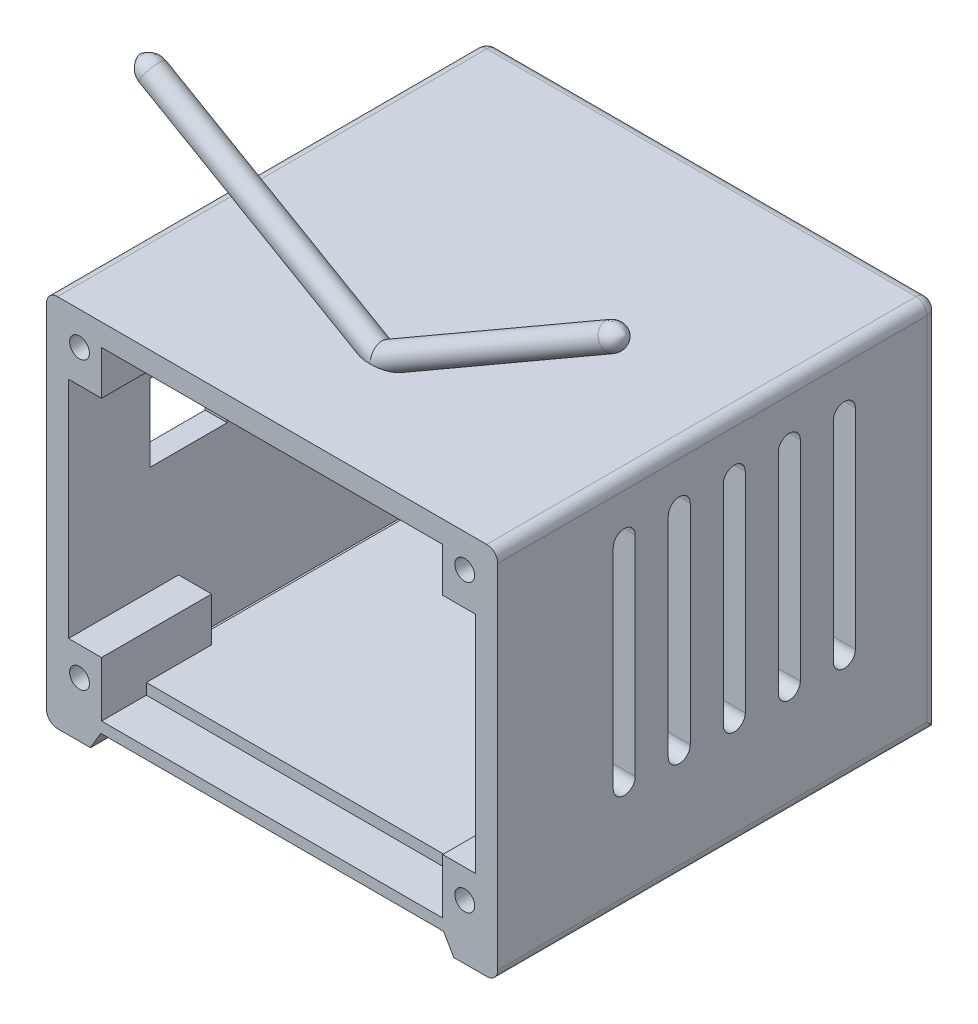
SolidWorks part; units mm, degrees
note: The reader was unsure of these and kept them because the rebuilt part matched: shared geometry of "草图12<3>".
ref_plane "前视基准面" through (0, 0, 0) normal (0, 0, 1) x (1, 0, 0)
ref_plane "上视基准面" through (0, 0, 0) normal (0, 1, 0) x (1, 0, 0)
ref_plane "右视基准面" through (0, 0, 0) normal (1, 0, 0) x (0, 0, -1)
sketch "草图1" plane through (0, 0, 0) normal (0, 0, 1) x (1, 0, 0)
  line L0 (0.8846, 17.8495) -> (0.8846, -40.3104) construction
  line L1 (-19.6154, 11.4554) -> (21.3846, 11.4554)
  line L2 (-19.6154, 11.4554) -> (-19.6154, -22.5446)
  line L4 (21.3846, 11.4554) -> (21.3846, -22.5446)
  line L5 (-19.6154, -22.5446) -> (-15.6154, -22.5446)
  line L6 (-15.6154, -22.5446) -> (-14.6916, -20.9446)
  line L7 (-14.6916, -20.9446) -> (16.4609, -20.9446)
  line L8 (21.3846, -22.5446) -> (17.3846, -22.5446)
  line L9 (17.3846, -22.5446) -> (16.4609, -20.9446)
  point P11 (0.8846, -20.9446)
  point P12 (0.2131, -20.9446)
  dimension "D1" = 34
  dimension "D2" = 41
  dimension "D3" = 4
  dimension "D4" = 120
  dimension "D5" = 1.6
extrude "凸台-拉伸1" add sketch "草图1" along normal blind 40
shell "抽壳1" thickness 2
sketch "草图2" plane through (21.3846, 0, 0) normal (1, 0, 0) x (0, 0, -1)
  line L0 (-28.5067, 6.4554) -> (-28.5067, -12.5446) construction
  line L1 (-27.5067, 6.4554) -> (-27.5067, -12.5446)
  line L2 (-29.5067, 6.4554) -> (-29.5067, -12.5446)
  line L3 (-23.5067, 6.4554) -> (-23.5067, -12.5446) construction
  line L4 (-22.5067, 6.4554) -> (-22.5067, -12.5446)
  line L5 (-24.5067, 6.4554) -> (-24.5067, -12.5446)
  line L6 (-18.5067, 6.4554) -> (-18.5067, -12.5446) construction
  line L7 (-17.5067, 6.4554) -> (-17.5067, -12.5446)
  line L8 (-19.5067, 6.4554) -> (-19.5067, -12.5446)
  line L9 (-13.5067, 6.4554) -> (-13.5067, -12.5446) construction
  line L10 (-12.5067, 6.4554) -> (-12.5067, -12.5446)
  line L11 (-14.5067, 6.4554) -> (-14.5067, -12.5446)
  line L12 (-8.5067, 6.4554) -> (-8.5067, -12.5446) construction
  line L13 (-7.5067, 6.4554) -> (-7.5067, -12.5446)
  line L14 (-9.5067, 6.4554) -> (-9.5067, -12.5446)
  line L15 (-40, 11.4554) -> (0, 11.4554) construction
  line L16 (-40, -22.5446) -> (0, -22.5446) construction
  arc A0 (-27.5067, 6.4554) -> (-29.5067, 6.4554) centre (-28.5067, 6.4554) ccw
  arc A1 (-29.5067, -12.5446) -> (-27.5067, -12.5446) centre (-28.5067, -12.5446) ccw
  arc A2 (-22.5067, 6.4554) -> (-24.5067, 6.4554) centre (-23.5067, 6.4554) ccw
  arc A3 (-24.5067, -12.5446) -> (-22.5067, -12.5446) centre (-23.5067, -12.5446) ccw
  arc A4 (-17.5067, 6.4554) -> (-19.5067, 6.4554) centre (-18.5067, 6.4554) ccw
  arc A5 (-19.5067, -12.5446) -> (-17.5067, -12.5446) centre (-18.5067, -12.5446) ccw
  arc A6 (-12.5067, 6.4554) -> (-14.5067, 6.4554) centre (-13.5067, 6.4554) ccw
  arc A7 (-14.5067, -12.5446) -> (-12.5067, -12.5446) centre (-13.5067, -12.5446) ccw
  arc A8 (-7.5067, 6.4554) -> (-9.5067, 6.4554) centre (-8.5067, 6.4554) ccw
  arc A9 (-9.5067, -12.5446) -> (-7.5067, -12.5446) centre (-8.5067, -12.5446) ccw
  point P2 (-28.5067, -3.0446)
  point P11 (-23.5067, -3.0446)
  point P18 (-18.5067, -3.0446)
  point P25 (-13.5067, -3.0446)
  point P32 (-8.5067, -3.0446)
  dimension "D2" = 2
  dimension "D3" = 5
  dimension "D4" = 10
  dimension "D1" = 5
extrude "切除-拉伸1" cut sketch "草图2" against normal up to next
sketch "草图3" plane through (-19.6154, 0, 0) normal (-1, 0, 0) x (0, 0, 1)
  line L1 (32.588, 1.8231) -> (25.588, 1.8231)
  line L2 (32.588, 1.8231) -> (32.588, -5.1769)
  line L3 (32.588, -5.1769) -> (25.588, -5.1769)
  line L4 (25.588, 1.8231) -> (25.588, -5.1769)
  dimension "D1" = 7
  dimension "D2" = 7
extrude "切除-拉伸2" cut sketch "草图3" against normal up to next
sketch "草图4" plane through (0, 0, 0) normal (0, 0, -1) x (-1, 0, 0)
  line L2 (4.6154, -17.3651) -> (-7.3846, -17.3651)
  line L3 (-7.3846, -17.3651) -> (-7.3846, -13.3651)
  line L4 (-7.3846, -13.3651) -> (4.6154, -13.3651)
  line L5 (4.6154, -13.3651) -> (4.6154, -17.3651)
  line L6 (19.6154, 11.4554) -> (19.6154, -22.5446) construction
  dimension "D1" = 12
  dimension "D2" = 4
  dimension "D3" = 15
extrude "切除-拉伸3" cut sketch "草图4" against normal blind 40 contours L4 L5 L2 L3
fillet "圆角1" radius 1 10 edges at (16.9227, -21.7446, 0) (-15.1535, -21.7446, 0) (0.8846, -20.9446, 0) (-19.6154, -5.5446, 0) (21.3846, -5.5446, 0) (0.8846, 11.4554, 0) (21.3846, 11.4554, 20) (21.3846, -22.5446, 20) (-19.6154, -22.5446, 20) (-19.6154, 11.4554, 20)
ref_plane "基准面4" through (0, 0, 30) normal (0, 0, 1) x (1, 0, 0)
sketch "草图5" plane through (0, 0, 30) normal (0, 0, 1) x (1, 0, 0)
  line L0 (0.8846, 11.4554) -> (0.8846, 30.3295) construction
  line L1 (20.3846, 11.4554) -> (-18.6154, 11.4554) construction
  line L4 (21.186, 24.4554) -> (0.8846, 12.7344)
  line L5 (-0.223, 12.0949) -> (-1.3306, 11.4554)
  line L7 (1.9922, 12.0949) -> (22.9816, 24.2131)
  line L12 (-0.223, 12.0949) -> (0.8846, 12.7344)
  line L13 (-1.3306, 11.4554) -> (0.8846, 11.4554)
  line L14 (0.8846, 11.4554) -> (1.9922, 12.0949)
  arc A1 (21.186, 24.4554) -> (22.9816, 24.2131) centre (21.927, 23.172) cw
  dimension "D1" = 13
  dimension "D2" = 30
sketch "草图7" plane through (0, 0, 30) normal (0, 0, 1) x (1, 0, 0)
  line L0 (0.8846, 12.7344) -> (-19.4168, 24.4554)
  line L1 (-21.2123, 24.2131) -> (-0.223, 12.0949)
  line L3 (0.8846, 11.4554) -> (3.0999, 11.4554)
  line L4 (-0.223, 12.0949) -> (0.8846, 11.4554)
  line L6 (3.0999, 11.4554) -> (0.8846, 12.7344)
  arc A0 (-19.4168, 24.4554) -> (-21.2123, 24.2131) centre (-20.1577, 23.172) ccw
revolve "旋转2" add sketch "草图7" angle 360 about L1
revolve "旋转3" add sketch "草图5" angle 360 about L7
sketch "草图8" plane through (0, 0, 40) normal (0, 0, 1) x (1, 0, 0)
  line L0 (-14.6154, 10.4554) -> (-14.6154, 5.4554)
  line L2 (-14.6154, 5.4554) -> (-19.6154, 5.4554)
  line L3 (-19.6154, 10.4554) -> (-19.6154, -21.5446) construction
  line L4 (-19.6154, -14.9446) -> (-14.6154, -14.9446)
  line L5 (-14.6154, -14.9446) -> (-14.6154, -20.9446)
  line L6 (-14.6916, -20.9446) -> (16.4609, -20.9446) construction
  line L7 (-14.6154, -20.9446) -> (-19.6154, -20.9446)
  line L8 (-19.6154, -20.9446) -> (-19.6154, -14.9446)
  line L9 (-19.6154, 10.4554) -> (-17.9387, 10.4554)
  line L10 (-19.6154, 10.4554) -> (-19.6154, 5.4554)
  line L11 (0.8846, 11.4554) -> (0.8846, 17.6402) construction
  line L12 (20.3846, 11.4554) -> (-18.6154, 11.4554) construction
  line L13 (0.8846, 17.6402) -> (0.8846, -33.7536) construction
  line L14 (21.3846, 10.4554) -> (21.3846, 5.4554)
  line L15 (21.3846, 10.4554) -> (19.7079, 10.4554)
  line L16 (21.3846, -20.9446) -> (21.3846, -14.9446)
  line L17 (16.3846, -20.9446) -> (21.3846, -20.9446)
  line L18 (16.3846, -14.9446) -> (16.3846, -20.9446)
  line L19 (21.3846, -14.9446) -> (16.3846, -14.9446)
  line L20 (16.3846, 5.4554) -> (21.3846, 5.4554)
  line L21 (16.3846, 10.4554) -> (16.3846, 5.4554)
  line L47 (-15.6293, 10.4554) -> (-14.6154, 10.4554)
  line L48 (-17.9387, 10.4554) -> (-15.6293, 10.4554)
  line L49 (17.3985, 10.4554) -> (19.7079, 10.4554)
  line L50 (17.3985, 10.4554) -> (16.3846, 10.4554)
  dimension "D1" = 5
  dimension "D2" = 5
  dimension "D6" = 5
  dimension "D7" = 6
extrude "凸台-拉伸3" add sketch "草图8" against normal blind 10
sketch "草图12" plane through (0, -18.9446, 0) normal (0, 1, 0) x (1, 0, 0)
  line L0 (21.3846, -1) -> (21.3846, -40) construction
  line L1 (20.3846, -1) -> (-18.6154, -1) construction
  circle A0 centre (7.3846, -4) radius 1.5
  dimension "D1" = 3
  dimension "D2" = 14
  dimension "D3" = 3
extrude "切除-拉伸6" cut sketch "草图12" against normal blind 7 and the other way blind 2 contours A0
sketch "草图14" plane through (0, -18.9446, 0) normal (0, 1, 0) x (1, 0, 0)
  line L0 (21.3846, -1) -> (21.3846, -40) construction
  line L1 (-18.6154, 0) -> (20.3846, 0) construction
  circle A0 centre (7.3846, -4) radius 2.5
  dimension "D3" = 5
  dimension "D1" = 14
  dimension "D2" = 4
extrude "凸台-拉伸4" add sketch "草图14" along normal blind 1
extrude "切除-拉伸7" cut sketch "草图12<3>" against normal blind 1 and the other way blind 3
sketch "草图12<3>" plane through (0, -18.9446, 0) normal (0, 1, 0) x (1, 0, 0) same geometry as "草图12"
sketch "草图15" plane through (0, 0, 0) normal (0, 0, -1) x (-1, 0, 0)
  text T0 "yangyi999"
extrude "凸台-拉伸5" add sketch "草图15" along normal blind 1
sketch "草图16" plane through (0, 0, 40) normal (0, 0, 1) x (1, 0, 0)
  line L0 (20.3846, 11.4554) -> (-18.6154, 11.4554) construction
  line L1 (-19.6154, 10.4554) -> (-19.6154, -21.5446) construction
  line L2 (21.3846, -21.5446) -> (21.3846, 10.4554) construction
  line L3 (-18.6154, -22.5446) -> (-15.6154, -22.5446) construction
  line L4 (17.3846, -22.5446) -> (20.3846, -22.5446) construction
  circle A0 centre (-16.6154, 8.4554) radius 0.9
  circle A1 centre (18.3846, 8.4554) radius 0.9
  circle A2 centre (-16.6154, -17.5446) radius 0.9
  circle A3 centre (18.3846, -17.5446) radius 0.9
  dimension "D1" = 1.8
  dimension "D2" = 1.8
  dimension "D3" = 1.8
  dimension "D4" = 1.8
  dimension "D7" = 3
  dimension "D8" = 3
  dimension "D9" = 3
  dimension "D10" = 5
  dimension "D11" = 3
  dimension "D12" = 5
  dimension "D5" = 3
  dimension "D6" = 3
extrude "切除-拉伸8" cut sketch "草图16" against normal blind 5
sketch "草图17" plane through (0, -18.9446, 0) normal (0, 1, 0) x (1, 0, 0)
  line L0 (-14.6154, -40) -> (-14.6154, -35.9251)
  line L1 (-14.6154, -35.9251) -> (16.3846, -35.9251)
  line L3 (0.8846, -40) -> (0.8846, -24.2871) construction
  line L4 (20.3846, -40) -> (-18.6154, -40) construction
  line L5 (-14.6154, -40) -> (0.8846, -40)
  line L7 (16.3846, -40) -> (16.3846, -35.9251)
  line L8 (0.8846, -40) -> (16.3846, -40)
extrude "切除-拉伸9" cut sketch "草图17" against normal blind 1
